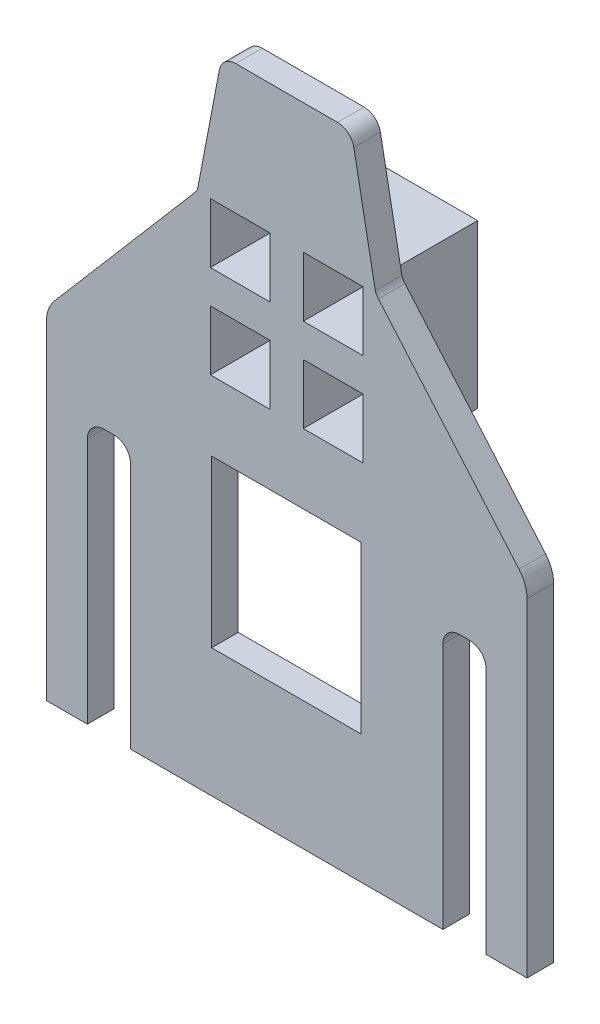
SolidWorks part; units mm, degrees
ref_plane "Front Plane" through (0, 0, 0) normal (0, 0, 1) x (1, 0, 0)
ref_plane "Top Plane" through (0, 0, 0) normal (0, 1, 0) x (1, 0, 0)
ref_plane "Right Plane" through (0, 0, 0) normal (1, 0, 0) x (0, 0, -1)
sketch "Sketch1" plane through (0, 0, 0) normal (0, 0, 1) x (1, 0, 0)
  line L4 (70, 309.9858) -> (85.2992, 309.9858)
  line L6 (43.2101, 271.7903) -> (49.7246, 305.9232)
  line L7 (42.2614, 270.1156) -> (0.0495, 220.7861)
  line L8 (0.0495, 220.7861) -> (42.9, 220.7861) construction
  line L9 (42.9, 220.7861) -> (42.9, 270.8599) construction
  line L10 (96.9829, 220.8599) -> (96.9829, 270.8599) construction
  line L11 (112.4871, 25.7747) -> (89.3829, 25.7747) construction
  line L12 (27.5129, 25.7747) -> (50.5, 25.7747) construction
  line L13 (25.2828, 25.7823) -> (2.6386, 25.8599)
  line L14 (96.6727, 271.7903) -> (90.212, 305.9159)
  line L15 (70, 329.5221) -> (70, -78.2612) construction
  line L18 (50.5, 25.7747) -> (50.5, 0) construction
  line L19 (70, 309.9858) -> (54.636, 309.9858)
  line L20 (135.9829, 220.8599) -> (96.9829, 220.8599) construction
  line L21 (139.9505, 220.7861) -> (135.9829, 220.8599) construction
  line L25 (89.3829, 25.7747) -> (89.3829, 0) construction
  line L27 (89.3829, 0) -> (50.5, 0)
  line L28 (15.2188, 54.8072) -> (17.7021, 54.8072)
  line L35 (125.0395, 54.8072) -> (122.0396, 54.8072)
  line L36 (122.0396, 194.8072) -> (125.0395, 194.8072)
  line L37 (117.0396, 59.8072) -> (117.0396, 189.8072)
  line L38 (130.0395, 189.8072) -> (130.0395, 59.8072)
  line L39 (142.3614, 214.274) -> (142.3614, 30.8599)
  line L40 (97.6215, 270.1156) -> (139.9505, 220.7861)
  line L41 (-2.3614, 214.274) -> (-2.3614, 30.8599)
  line L42 (9.9605, 189.8072) -> (9.9605, 60.0656)
  line L43 (22.9604, 60.0656) -> (22.9604, 189.8072)
  line L44 (17.9604, 194.8072) -> (14.9605, 194.8072)
  line L45 (28.9972, 24.1103) -> (50.5, 0)
  line L46 (114.7172, 25.7823) -> (137.3614, 25.8599)
  line L47 (89.3829, 0) -> (111.0028, 24.1103)
  arc A1 (42.2614, 270.1156) -> (43.2101, 271.7903) centre (38.4667, 273.3715) ccw
  arc A5 (97.6215, 270.1156) -> (96.6727, 271.7903) centre (101.4161, 273.3715) cw
  arc A8 (137.3614, 25.8599) -> (142.3614, 30.8599) centre (137.3614, 30.8599) ccw
  arc A9 (2.6386, 25.8599) -> (-2.3614, 30.8599) centre (2.6386, 30.8599) cw
  arc A10 (49.7246, 305.9232) -> (54.636, 309.9858) centre (54.636, 304.9858) cw
  arc A11 (85.2992, 309.9858) -> (90.212, 305.9159) centre (85.2992, 304.9858) cw
  arc A12 (139.9505, 220.7861) -> (142.3614, 214.274) centre (132.3614, 214.274) cw
  arc A13 (0.0495, 220.7861) -> (-2.3614, 214.274) centre (7.6386, 214.274) ccw
  arc A14 (25.2828, 25.7823) -> (28.9972, 24.1103) centre (25.2657, 20.7823) cw
  arc A15 (114.7172, 25.7823) -> (111.0028, 24.1103) centre (114.7343, 20.7823) ccw
  arc A16 (17.9604, 194.8072) -> (22.9604, 189.8072) centre (17.9604, 189.8072) cw
  arc A17 (9.9605, 189.8072) -> (14.9605, 194.8072) centre (14.9605, 189.8072) cw
  arc A18 (125.0395, 54.8072) -> (130.0395, 59.8072) centre (125.0395, 59.8072) ccw
  arc A19 (122.0396, 54.8072) -> (117.0396, 59.8072) centre (122.0396, 59.8072) cw
  arc A20 (125.0395, 194.8072) -> (130.0395, 189.8072) centre (125.0395, 189.8072) cw
  arc A21 (117.0396, 189.8072) -> (122.0396, 194.8072) centre (122.0396, 189.8072) cw
  arc A22 (17.7021, 54.8072) -> (22.9604, 60.0656) centre (17.7021, 60.0656) ccw
  arc A23 (15.2188, 54.8072) -> (9.9605, 60.0656) centre (15.2188, 60.0656) cw
  point P18 (22.9604, 194.8072)
  point P51 (9.9605, 194.8072)
  point P57 (130.0395, 54.8072)
  point P61 (117.0396, 54.8072)
  point P67 (130.0395, 194.8072)
  point P70 (117.0396, 194.8072)
  point P77 (22.9604, 54.8072)
  point P80 (9.9605, 54.8072)
  dimension "D1" = 5
  dimension "D2" = 5
  dimension "D3" = 5
  dimension "D4" = 10
  dimension "D5" = 5
  dimension "D6" = 5
  dimension "D7" = 5.2583
extrude "Boss-Extrude1" add sketch "Sketch1" along normal blind 8
sketch "Sketch2" plane through (0, 0, 8) normal (0, 0, 1) x (1, 0, 0)
  line L2 (92.3829, 204.0089) -> (47.3829, 204.0089)
  line L8 (47.3829, 204.0089) -> (47.3829, 154.0089)
  line L9 (47.3829, 154.0089) -> (92.3829, 154.0089)
  line L10 (92.3829, 204.0089) -> (92.3829, 154.0089)
extrude "Cut-Extrude1" cut sketch "Sketch2" against normal through all contours L10 L2 L8 L9 region at (69.8829, 179.0089, 8)
sketch "Sketch3" plane through (0, 0, 0) normal (0, 0, -1) x (-1, 0, 0)
  line L1 (-142.3614, 115.3599) -> (2.3614, 115.3599)
  line L3 (-142.3614, 30.8599) -> (-142.3614, 214.274) construction
  line L6 (2.3614, 214.274) -> (2.3614, 30.8599) construction
split "Split1" trim tools "Sketch3" bodies to split 102 resulting bodies 104 108
ref_plane "Plane4" through (0, 115.3599, 0) normal (0, 1, 0) x (1, 0, 0)
sketch "Sketch4" plane through (0, 115.3599, 0) normal (0, -1, 0) x (-1, 0, 0)
  line L0 (-3.7995, -8) -> (-3.7995, -4)
  line L2 (2.3614, -8) -> (-9.9605, -8) construction
  circle A1 centre (-70, -4) radius 2.5
  circle A2 centre (-40, -4) radius 2.5
  circle A3 centre (-100, -4) radius 2.5
  circle A5 centre (-137.3614, -4) radius 2.5
  circle A6 centre (-3.7995, -4) radius 2.5
sketch "Sketch5" plane through (0, 115.3599, -115.3599) normal (0, -1, 0) x (1, 0, 0)
  circle A1 centre (70, 119.3599) radius 2.5
  circle A2 centre (100, 119.3599) radius 2.5
  circle A3 centre (40, 119.3599) radius 2.5
  circle A5 centre (2.6386, 119.3599) radius 2.5
  circle A6 centre (137.3614, 119.3599) radius 2.5
extrude "Cut-Extrude6" cut sketch "Sketch5" along direction (0, -1, 0) on the side of the normal blind 5.2 contours A5 | A3 | A1
extrude "Cut-Extrude7" cut sketch "Sketch4" against normal blind 10 contours A2 | A6 | A1 | A3 | A5 region at (70, 115.3599, 4) region at (40, 115.3599, 4) region at (100, 115.3599, 4) region at (2.0817, 115.3599, 5.7178)
delete or keep bodies "Body-Delete/Keep 3" type delete bodies bodies 106
sketch "Sketch6" plane through (0, 0, 8) normal (0, 0, 1) x (1, 0, 0)
  circle A0 centre (50.0001, 267.9803) radius 1.5
  circle A1 centre (90.0001, 267.9803) radius 1.5
  circle A2 centre (90.0001, 227.9803) radius 1.5
  circle A3 centre (50.0001, 227.9803) radius 1.5
extrude "Cut-Extrude8" cut sketch "Sketch6" against normal through all
sketch "Sketch7" plane through (0, 0, 0) normal (0, 0, -1) x (-1, 0, 0)
  line L10 (-94.5001, 223.4803) -> (-94.5001, 272.4803)
  line L11 (-47.0001, 270.9803) -> (-47.0001, 252.9803)
  line L12 (-45.5001, 272.4803) -> (-45.5001, 223.4803)
  line L13 (-45.5001, 223.4803) -> (-94.5001, 223.4803)
  line L14 (-93.0001, 270.9803) -> (-75.0001, 270.9803)
  line L15 (-93.0001, 224.9803) -> (-75.0001, 224.9803)
  line L16 (-93.0001, 224.9803) -> (-93.0001, 242.9803)
  line L18 (-65.0001, 270.9803) -> (-65.0001, 252.9803)
  line L19 (-65.0001, 224.9803) -> (-47.0001, 224.9803)
  line L20 (-45.5001, 272.4803) -> (-94.5001, 272.4803)
  line L21 (-75.0001, 270.9803) -> (-75.0001, 252.9803)
  line L22 (-47.0001, 252.9803) -> (-65.0001, 252.9803)
  line L23 (-47.0001, 242.9803) -> (-47.0001, 224.9803)
  line L24 (-93.0001, 242.9803) -> (-75.0001, 242.9803)
  line L25 (-65.0001, 270.9803) -> (-47.0001, 270.9803)
  line L26 (-75.0001, 252.9803) -> (-93.0001, 252.9803)
  line L27 (-65.0001, 242.9803) -> (-47.0001, 242.9803)
  line L28 (-65.0001, 242.9803) -> (-65.0001, 224.9803)
  line L29 (-75.0001, 242.9803) -> (-75.0001, 224.9803)
  line L30 (-93.0001, 252.9803) -> (-93.0001, 270.9803)
extrude "Boss-Extrude2" add sketch "Sketch7" along normal blind 15
sketch "Sketch8" plane through (0, 0, -15) normal (0, 0, -1) x (-1, 0, 0)
  line L0 (-45.5001, 272.4803) -> (-94.5001, 272.4803)
  line L1 (-94.5001, 272.4803) -> (-94.5001, 223.4803)
  line L2 (-94.5001, 223.4803) -> (-45.5001, 223.4803)
  line L3 (-94.5001, 223.4803) -> (-45.5001, 223.4803) construction
  line L4 (-94.5001, 223.4803) -> (-45.5001, 223.4803) construction
  line L5 (-45.5001, 223.4803) -> (-45.5001, 272.4803)
  circle A0 centre (-50.0001, 267.9803) radius 1.5
  circle A1 centre (-90.0001, 267.9803) radius 1.5
  circle A2 centre (-50.0001, 227.9803) radius 1.5
  circle A3 centre (-90.0001, 227.9803) radius 1.5
extrude "Boss-Extrude3" add sketch "Sketch8" along normal blind 10
sketch "Sketch9" plane through (0, 0, 8) normal (0, 0, 1) x (1, 0, 0)
  line L9 (45.5001, 272.4803) -> (94.5001, 272.4803)
  line L10 (45.5001, 272.4803) -> (45.5001, 223.4803)
  line L11 (45.5001, 223.4803) -> (94.5001, 223.4803)
  line L12 (94.5001, 272.4803) -> (94.5001, 223.4803)
extrude "Cut-Extrude9" cut sketch "Sketch9" against normal blind 8
sketch "Sketch10" plane through (0, 0, 0) normal (0, 0, 1) x (1, 0, 0)
  line L17 (94.5001, 223.4803) -> (45.5001, 223.4803)
  line L18 (45.5001, 223.4803) -> (45.5001, 224.9803)
  line L19 (45.5001, 272.4803) -> (45.5001, 223.4803) construction
  line L23 (47.0001, 242.9803) -> (65.0001, 242.9803)
  line L24 (47.0001, 242.9803) -> (47.0001, 224.9803)
  line L26 (47.0001, 224.9803) -> (65.0001, 224.9803)
  line L27 (65.0001, 242.9803) -> (65.0001, 224.9803)
  line L29 (45.5001, 223.4803) -> (45.5001, 272.4803) construction
  line L30 (45.5001, 242.9803) -> (45.5001, 224.9803)
  line L31 (45.5001, 272.4803) -> (94.5001, 272.4803)
  line L32 (94.5001, 272.4803) -> (94.5001, 223.4803)
  line L40 (75.0001, 242.9803) -> (93.0001, 242.9803)
  line L41 (75.0001, 242.9803) -> (75.0001, 224.9803)
  line L42 (75.0001, 224.9803) -> (93.0001, 224.9803)
  line L43 (93.0001, 242.9803) -> (93.0001, 224.9803)
  line L44 (75.0001, 270.9803) -> (93.0001, 270.9803)
  line L45 (75.0001, 270.9803) -> (75.0001, 252.9803)
  line L46 (75.0001, 252.9803) -> (93.0001, 252.9803)
  line L47 (93.0001, 270.9803) -> (93.0001, 252.9803)
  line L48 (47.0001, 270.9803) -> (65.0001, 270.9803)
  line L49 (47.0001, 270.9803) -> (47.0001, 252.9803)
  line L50 (47.0001, 252.9803) -> (65.0001, 252.9803)
  line L51 (65.0001, 270.9803) -> (65.0001, 252.9803)
  line M21 (93.0001, 224.9803) -> (75.0001, 224.9803)
  line M22 (75.0001, 224.9803) -> (75.0001, 242.9803)
  line M23 (75.0001, 242.9803) -> (93.0001, 242.9803)
  line M24 (93.0001, 242.9803) -> (93.0001, 224.9803)
  line M25 (65.0001, 224.9803) -> (47.0001, 224.9803)
  line M26 (47.0001, 224.9803) -> (47.0001, 242.9803)
  line M27 (47.0001, 242.9803) -> (65.0001, 242.9803)
  line M28 (65.0001, 242.9803) -> (65.0001, 224.9803)
  line M29 (65.0001, 270.9803) -> (65.0001, 252.9803)
  line M30 (65.0001, 252.9803) -> (47.0001, 252.9803)
  line M31 (47.0001, 252.9803) -> (47.0001, 270.9803)
  line M32 (47.0001, 270.9803) -> (65.0001, 270.9803)
  line M33 (93.0001, 252.9803) -> (75.0001, 252.9803)
  line M34 (75.0001, 252.9803) -> (75.0001, 270.9803)
  line M35 (75.0001, 270.9803) -> (93.0001, 270.9803)
  line M36 (93.0001, 270.9803) -> (93.0001, 252.9803)
  line M37 (45.5001, 272.4803) -> (45.5001, 223.4803)
  line M38 (45.5001, 223.4803) -> (94.5001, 223.4803)
  line M39 (94.5001, 223.4803) -> (94.5001, 272.4803)
  line M40 (94.5001, 272.4803) -> (45.5001, 272.4803)
extrude "Boss-Extrude4" add sketch "Sketch10" along normal blind 8 contours M40 M37 M38 M39 M36 M33 M34 M35 M32 M29 M30 M31 M28 M25 M26 M27 M24 M21 M22 M23 region at (70.0001, 247.9803, 0)
